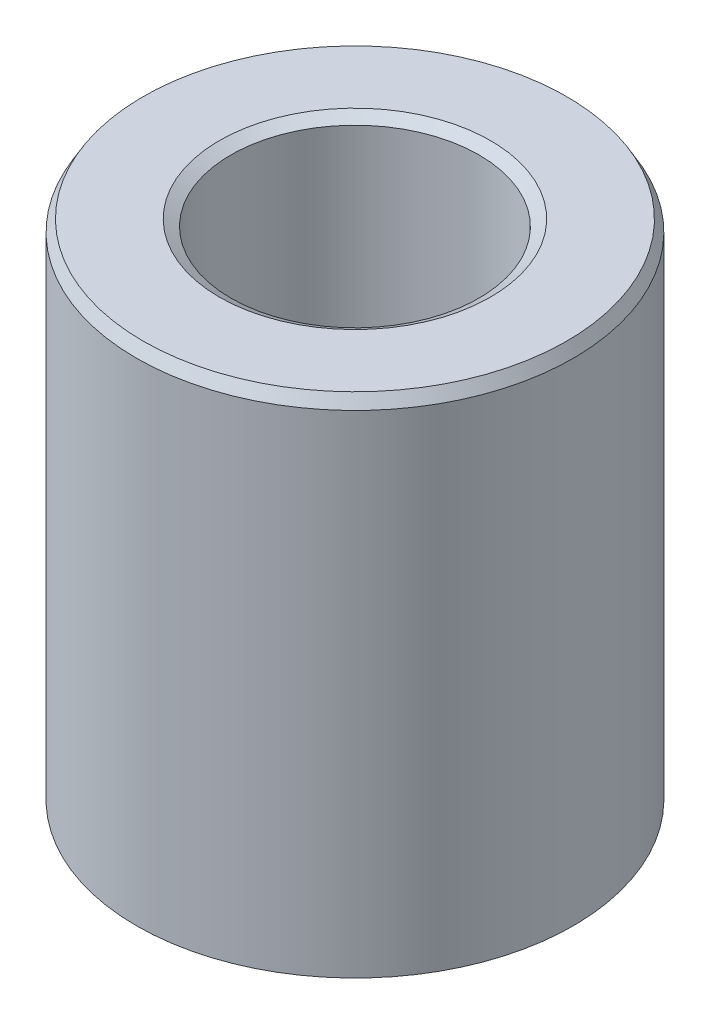
SolidWorks part; units mm, degrees
ref_plane "Front Plane" through (0, 0, 0) normal (0, 0, 1) x (1, 0, 0)
ref_plane "Top Plane" through (0, 0, 0) normal (0, 1, 0) x (1, 0, 0)
ref_plane "Right Plane" through (0, 0, 0) normal (1, 0, 0) x (0, 0, -1)
sketch "Sketch1" plane through (0, 0, 0) normal (0, 1, 0) x (1, 0, 0)
  circle A0 centre (0, 0) radius 52.5
  dimension "SLEEVE_OD" = 105
extrude "Boss-Extrude1" add sketch "Sketch1" along normal blind 122.4993
sketch "Sketch2" plane through (0, 0, 0) normal (0, 1, 0) x (1, 0, 0)
  circle A0 centre (0, 0) radius 29.8242
  dimension "BORE_D" = 59.6484
extrude "Cut-Extrude1" cut sketch "Sketch2" along normal through all
chamfer "Chamfer1" distance 2.7654 angle 30 4 edges at (0, 122.4993, 29.8242) (0, 0, 29.8242) (0, 0, 52.5) (0, 122.4993, 52.5) first distance on face at (0, 122.4993, 29.8242) first distance on face at (0, 0, 29.8242) first distance on face at (0, 122.4993, 52.5)
